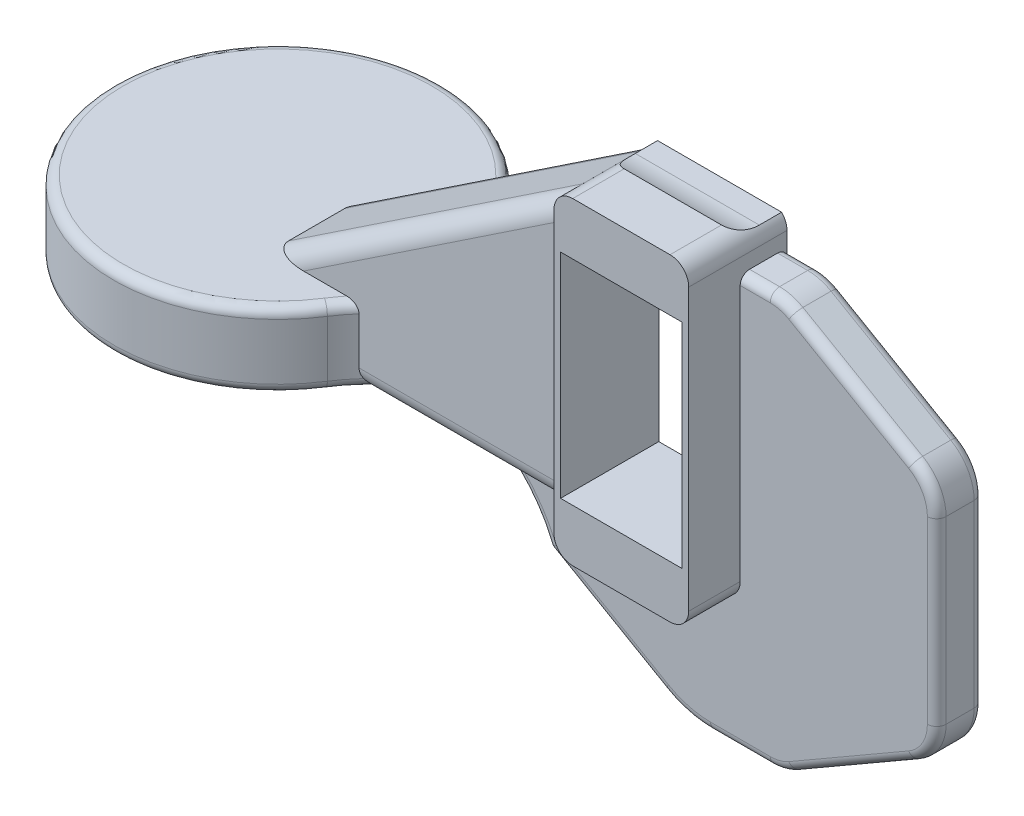
SolidWorks part; units mm, degrees
material "ABS"
ref_plane "Front Plane" through (0, 0, 0) normal (0, 0, 1) x (1, 0, 0)
ref_plane "Top Plane" through (0, 0, 0) normal (0, 1, 0) x (1, 0, 0)
ref_plane "Right Plane" through (0, 0, 0) normal (1, 0, 0) x (0, 0, -1)
other "Center of Mass"
sketch "Sketch1" plane through (0, 0, 0) normal (0, 1, 0) x (1, 0, 0)
  line L0 (0, 0) -> (128.1157, 0) construction
  line L2 (27.3861, -2.5) -> (82.5, -2.5)
  line L4 (27.3861, 2.5) -> (82.5, 2.5)
  line L5 (82.5, -2.5) -> (82.5, 2.5)
  arc A0 (14.7464, 9.4231) -> (14.7464, -9.4231) centre (0, 0) ccw
  arc A1 (27.3861, 2.5) -> (14.7464, 9.4231) centre (27.3861, 17.5) cw
  arc A2 (14.7464, -9.4231) -> (27.3861, -2.5) centre (27.3861, -17.5) cw
  point P3 (50, 0)
  dimension "D1" = 35
  dimension "D4" = 15
  dimension "D5" = 15
  dimension "D2" = 5
  dimension "D3" = 82.5
extrude "Boss-Extrude1" add sketch "Sketch1" along normal blind 8
sketch "Sketch4" plane through (82.5, 0, 0) normal (1, 0, 0) x (0, 0, -1)
  line L0 (0, 8) -> (0, 0) construction
  line L1 (-2.5, 8) -> (2.5, 8) construction
  line L3 (-2.5, -21) -> (2.5, -21)
  line L4 (-2.5, -21) -> (-2.5, 29)
  line L5 (-2.5, 29) -> (2.5, 29)
  line L6 (2.5, -21) -> (2.5, 29)
  line L7 (-2.5, -21) -> (2.5, 29) construction
  line L8 (-2.5, 29) -> (2.5, -21) construction
  point P5 (0, 4)
  dimension "D1" = 50
  dimension "D2" = 5
extrude "Boss-Extrude4" add sketch "Sketch4" against normal blind 50
fillet "Fillet1" radius 15 2 edges at (32.5, 0, 0) (32.5, 8, 0)
sketch "Sketch5" plane through (0, 0, 2.5) normal (0, 0, 1) x (1, 0, 0)
  line L0 (82.5, 4) -> (27.3861, 4) construction
  line L1 (82.5, 29) -> (82.5, -21) construction
  line L2 (27.3861, 11.7188) -> (27.3861, -3.7188) construction
  line L3 (57.5, 29) -> (57.5, -21) construction
  line L4 (32.5, 29) -> (82.5, 29) construction
  line L5 (32.5, -21) -> (82.5, -21) construction
  line L6 (54.9431, 4) -> (27.3861, 4) construction
  line L7 (32.5, 29) -> (32.5, 23) construction
  line L8 (32.5, 30.25) -> (57, 30.25)
  line L9 (32.5, 30.25) -> (32.5, -22.25)
  line L10 (32.5, -22.25) -> (57, -22.25)
  line L11 (57, 30.25) -> (57, -22.25)
  line L12 (32.5, 30.25) -> (57, -22.25) construction
  line L13 (32.5, -22.25) -> (57, 30.25) construction
  line L14 (44.75, -22.25) -> (44.75, 30.25) construction
  line L15 (38.25, 1.2) -> (51.25, 24) construction
  line L16 (38.25, 24) -> (51.25, 24)
  line L17 (38.25, 24) -> (38.25, 1.2)
  line L18 (38.25, 1.2) -> (51.25, 1.2)
  line L19 (51.25, 24) -> (51.25, 1.2)
  line L20 (38.25, 12.6) -> (51.25, 12.6) construction
  line L21 (51.95, -4.4) -> (37.55, -4.4)
  line L22 (51.95, -4.4) -> (51.95, 29.6)
  line L23 (51.95, 29.6) -> (37.55, 29.6)
  line L24 (37.55, -4.4) -> (37.55, 29.6)
  line L25 (51.95, -4.4) -> (37.55, 29.6) construction
  line L26 (51.95, 29.6) -> (37.55, -4.4) construction
  circle A0 centre (44.75, 18) radius 12.25
  circle A1 centre (44.75, -10) radius 12.25
  circle A2 centre (44.75, -10) radius 15.75
  circle A3 centre (64.9562, -1.2988) radius 1.5
  circle A4 centre (64.9562, -1.2988) radius 3
  circle A5 centre (64.9562, 9.2988) radius 3
  circle A6 centre (64.9562, 9.2988) radius 1.5
  circle A7 centre (44.75, -10) radius 1.5
  circle A8 centre (44.75, -10) radius 3
  point P13 (44.75, 4)
  point P30 (44.75, 12.6)
  dimension "D4" = 12.25
  dimension "D5" = 24.5
  dimension "D13" = 31.5
  dimension "D14" = 3
  dimension "D16" = 6
  dimension "D17" = 22
  dimension "D18" = 3
  dimension "D19" = 6
  dimension "D1" = 24.5
  dimension "D2" = 52.5
  dimension "D3" = 0
  dimension "D6" = 12.25
  dimension "D7" = 6
  dimension "D8" = 22.8
  dimension "D9" = 13
  dimension "D10" = 34
  dimension "D11" = 14.4
  dimension "D12" = 5.6
  dimension "D15" = 5.2988
sketch "Sketch6" plane through (0, 0, 2.5) normal (0, 0, 1) x (1, 0, 0)
  circle A0 centre (44.75, -10) radius 1.5
  dimension "D1" = 3
sketch "Sketch8" plane through (0, 0, 2.5) normal (0, 0, 1) x (1, 0, 0)
  line L0 (37.55, -4.4) -> (37.55, 29.6)
  line L1 (37.55, 29.6) -> (51.95, 29.6)
  line L2 (51.95, 29.6) -> (51.95, -4.4)
  line L3 (51.95, -4.4) -> (37.55, -4.4)
  dimension "D1" = 34
extrude "Boss-Extrude5" add sketch "Sketch8" along normal blind 5.5
sketch "Sketch9" plane through (0, 0, 8) normal (0, 0, 1) x (1, 0, 0)
  line L0 (38.25, 24) -> (51.25, 24)
  line L1 (51.25, 24) -> (51.25, 1.2)
  line L2 (51.25, 1.2) -> (38.25, 1.2)
  line L3 (38.25, 1.2) -> (38.25, 24)
extrude "Cut-Extrude2" cut sketch "Sketch9" against normal through all
fillet "Fillet2" radius 5 2 edges at (32.5, -21, 0) (32.5, 29, 0)
fillet "Fillet3" radius 2 4 edges at (51.95, -4.4, 5.25) (51.95, 29.6, 5.25) (37.55, 29.6, 5.25) (37.55, -4.4, 5.25)
fillet "Fillet4" radius 6 1 edges at (44.75, 29, 2.5)
sketch "Sketch14" plane through (0, 0, 2.5) normal (0, 0, 1) x (1, 0, 0)
  line L0 (72.9562, 29) -> (72.9562, -21)
  line L1 (82.5, -21) -> (28.5, -21)
  line L2 (82.5, -21) -> (82.5, -19.5)
  line L3 (56.5017, -18) -> (28.5, -18)
  line L4 (28.5, -21) -> (28.5, -18)
  line L5 (51.3783, 29) -> (82.5, 29) construction
  line L6 (56.5017, 26) -> (28.5, 26)
  line L7 (82.5, 4) -> (14.7464, 4) construction
  line L8 (14.7464, 8) -> (14.7464, 0) construction
  line L9 (51.3055, 29) -> (29.6549, 16.5)
  line L10 (29.6549, 16.5) -> (29.6549, -8.5)
  line L11 (29.6549, -8.5) -> (51.3055, -21)
  line L12 (51.3055, -21) -> (72.9562, -8.5)
  line L13 (72.9562, -8.5) -> (72.9562, 16.5)
  line L14 (72.9562, 16.5) -> (51.3055, 29)
  circle A0 centre (51.3055, 4) radius 21.6506 construction
  circle A1 centre (64.9562, 9.2988) radius 3 construction
  line M5 (32.5, -15) -> (32.5, -16)
  arc M6 (32.5, -16) -> (37.5, -21) centre (37.5, -16) ccw
  line M7 (37.5, -21) -> (82.5, -21)
  line M8 (82.5, -21) -> (82.5, 29)
  line M9 (82.5, 29) -> (51.3783, 29)
  arc M10 (51.3783, 29) -> (51.95, 27.6) centre (49.95, 27.6) cw
  line M11 (51.95, 27.6) -> (51.95, -2.4)
  line M15 (37.55, -2.4) -> (37.55, 27.6)
  arc M16 (37.55, 27.6) -> (38.1217, 29) centre (39.55, 27.6) cw
  line M17 (38.1217, 29) -> (37.5, 29)
  arc M18 (37.5, 29) -> (32.5, 24) centre (37.5, 24) ccw
  line M19 (32.5, 24) -> (32.5, 23)
  arc M20 (32.5, 23) -> (27.3861, 11.7188) centre (17.5, 23) cw
  arc M24 (27.3861, -3.7188) -> (32.5, -15) centre (17.5, -15) cw
  dimension "D4" = 8
  dimension "D6" = 25
  dimension "D1" = 3
  dimension "D2" = 8
  dimension "D3" = 54
  dimension "D5" = 0
extrude "Cut-Extrude6" cut sketch "Sketch14" against normal blind 10 contours L11 L3 M24 M5 M6 | L11 L3 M6 M7 | L12 L1 L0 | L11 L12 L3 | L0 M9 M7 M8 | L14 L0 M9 M10 | L6 L14 M10 M11 | L9 L6 M15 M18 M19 M20 | L6 M15 M16 M17 M18 region at (77.7281, 4, 2.5) region at (65.7396, 24.8332, 2.5) region at (65.7393, -16.8333, 2.5) region at (53.4314, 26.9107, 2.5) region at (51.3055, -19, 2.5) region at (41.4922, -19.5298, 2.5) region at (36.9232, -15.2513, 2.5) region at (34.7312, 22.5576, 2.5) region at (35.7594, 27.2757, 2.5)
fillet "Fillet5" radius 5 4 edges at (56.5017, 26, 0) (72.9562, 16.5, 0) (72.9562, -8.5, 0) (56.5017, -18, 0)
fillet "Fillet6" radius 10 1 edges at (46.1094, -18, 0)
ref_plane "Plane5" through (0, 0, 0) normal (0, 0, 1) x (1, 0, 0)
sketch "Sketch18" plane through (0, 0, 0) normal (0, 0, 1) x (1, 0, 0)
  line L0 (6.6848, 8) -> (6.6848, 0)
  line L1 (-17.5, 0) -> (14.7464, 0) construction
  line L2 (14.7464, 8) -> (-1.3768, 8) construction
  line L3 (6.6848, 0) -> (17.5, 0)
  line L4 (17.5, 0) -> (37.55, 0)
  line L5 (37.55, 21.0582) -> (37.55, -2.4) construction
  line L6 (37.55, 0) -> (37.55, 27.6)
  line L7 (14.7464, 8) -> (-17.5, 8) construction
  line L8 (-1.3768, 8) -> (-1.3768, 17.551) construction
  line L9 (-1.3768, 17.551) -> (14.7464, 17.551) construction
  line L10 (14.7464, 17.551) -> (14.7464, 8) construction
  line L11 (6.6848, 17.551) -> (6.6848, -15.9983) construction
  line L12 (38.1217, 29) -> (6.6848, 8)
  arc A0 (37.55, 27.6) -> (38.1217, 29) centre (39.55, 27.6) cw
  dimension "D1" = 17.551
extrude "Boss-Extrude7" add sketch "Sketch18" along normal blind 7.5 and the other way blind 2.5 separate body
fillet "Fillet7" radius 2 1 edges at (22.4032, 18.5, 7.5)
fillet "Fillet8" radius 2 1 edges at (22.4032, 18.5, -2.5)
fillet "Fillet9" radius 2 1 edges at (22.1174, 0, 7.5)
fillet "Fillet10" radius 1 29 edges at (53.556, 26, -2.5) (56.456, 25.8296, -2.5) (64.0591, 21.6368, -2.5) (72.2863, 16.1132, -2.5) (72.9562, 4, -2.5) (72.2863, -8.1132, -2.5) (64.0591, -13.6368, -2.5) (56.456, -17.8296, -2.5) (51.9754, -18, -2.5) (46.2007, -17.6593, -2.5) (53.556, 26, 2.5) (56.456, 25.8296, 2.5) (64.0591, 21.6368, 2.5) (72.2863, 16.1132, 2.5) (72.9562, 4, 2.5) (72.2863, -8.1132, 2.5) (64.0591, -13.6368, 2.5) (56.456, -17.8296, 2.5) (51.9754, -18, 2.5) (46.2007, -17.6593, 2.5) (29.7819, -6.3887, -2.5) (24.1319, -1.5457, -2.8573) (16.0098, 0, -7.7235) (-17.5, 0, 0) (16.0098, 0, 7.7235) (20.7542, -0.3573, 4.0457) (37.6321, -13.1056, -2.5) (37.6321, -13.1056, 2.5) (29.7819, -6.3887, 2.5)
fillet "Fillet11" radius 1 7 edges at (29.7819, 14.3887, -2.5) (20.7542, 8.3573, -4.0457) (16.0098, 8, -7.7235) (29.7819, 14.3887, 2.5) (24.1319, 9.5457, 2.8573) (16.0098, 8, 7.7235) (-17.5, 8, 0)
